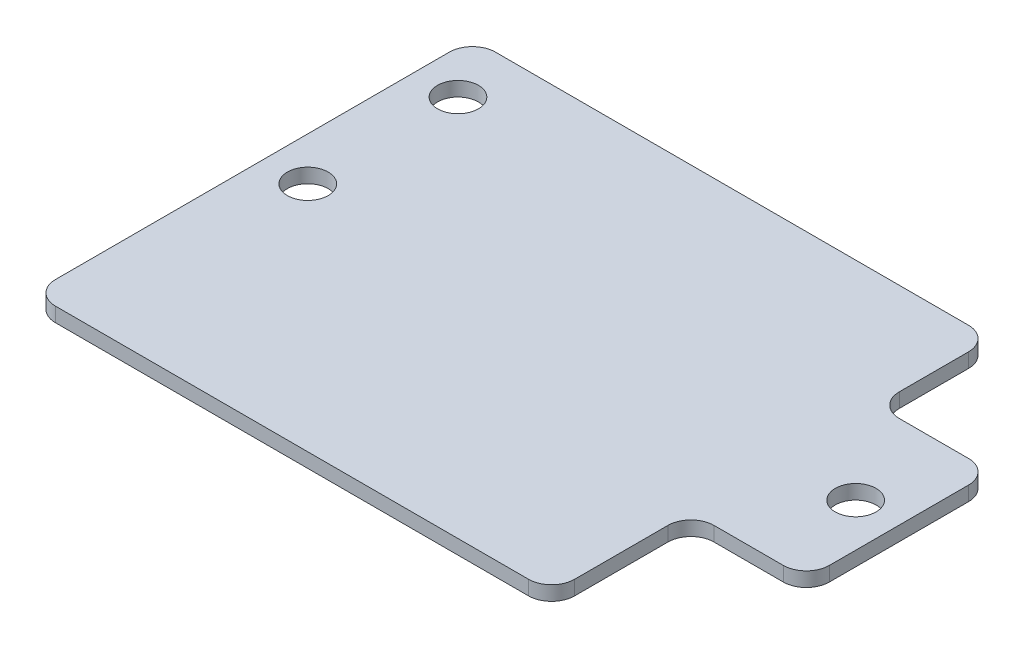
SolidWorks part; units mm, degrees
material "AISI Type A2 Tool Steel"
ref_plane "Front Plane" through (0, 0, 0) normal (0, 0, 1) x (1, 0, 0)
ref_plane "Top Plane" through (0, 0, 0) normal (0, 1, 0) x (1, 0, 0)
ref_plane "Right Plane" through (0, 0, 0) normal (1, 0, 0) x (0, 0, -1)
sketch "Sketch1" plane through (0, 0, 0) normal (0, 1, 0) x (1, 0, 0)
  line B0 (0, 0) -> (0, -48.4323)
  line B1 (0, -48.4323) -> (57.15, -48.4323)
  line B2 (57.15, -48.4323) -> (57.15, -33.0905)
  line B3 (57.15, -33.0905) -> (69.85, -33.0905)
  line B4 (69.85, -33.0905) -> (69.85, -12.7)
  line B5 (69.85, -12.7) -> (57.15, -12.7)
  line B6 (57.15, -12.7) -> (57.15, 0)
  line B7 (0, 0) -> (57.15, 0)
sketch_block_instance "Block-Armor-1"
sketch_block "Block-Armor" parameters "D1"=12.7
extrude "Boss-Extrude1" add sketch "Sketch1" along normal blind 1.5875
fillet "Fillet1" radius 2.54 8 edges at (0, 0.7937, 48.4323) (0, 0.7937, 0) (57.15, 0.7937, 0) (57.15, 0.7937, 48.4323) (69.85, 0.7937, 33.0905) (69.85, 0.7937, 12.7) (57.15, 0.7937, 33.0905) (57.15, 0.7937, 12.7)
sketch "Sketch2" plane through (0, 1.5875, 0) normal (0, 1, 0) x (1, 0, 0)
  line L0 (0, -2.54) -> (0, -45.8923) construction
  line L1 (69.85, -30.5505) -> (69.85, -15.24) construction
  line L2 (54.61, 0) -> (2.54, 0) construction
  circle A0 centre (4.7625, -6.35) radius 2.2479
  circle A1 centre (4.7625, -22.8854) radius 2.2479
  circle A2 centre (65.0748, -22.8854) radius 2.2479
  point P6 (0, 0)
  point P7 (0, 0)
  point P10 (0, 0)
  point P13 (4.7625, -23.2019)
  point P14 (4.7625, -18.3784)
  point P15 (4.7625, -26.5412)
  dimension "D1" = 4.4958
  dimension "D2" = 4.7625
  dimension "D3" = 16.5354
  dimension "D4" = 4.7752
  dimension "D5" = 6.35
extrude "Cut-Extrude1" cut sketch "Sketch2" against normal through all
